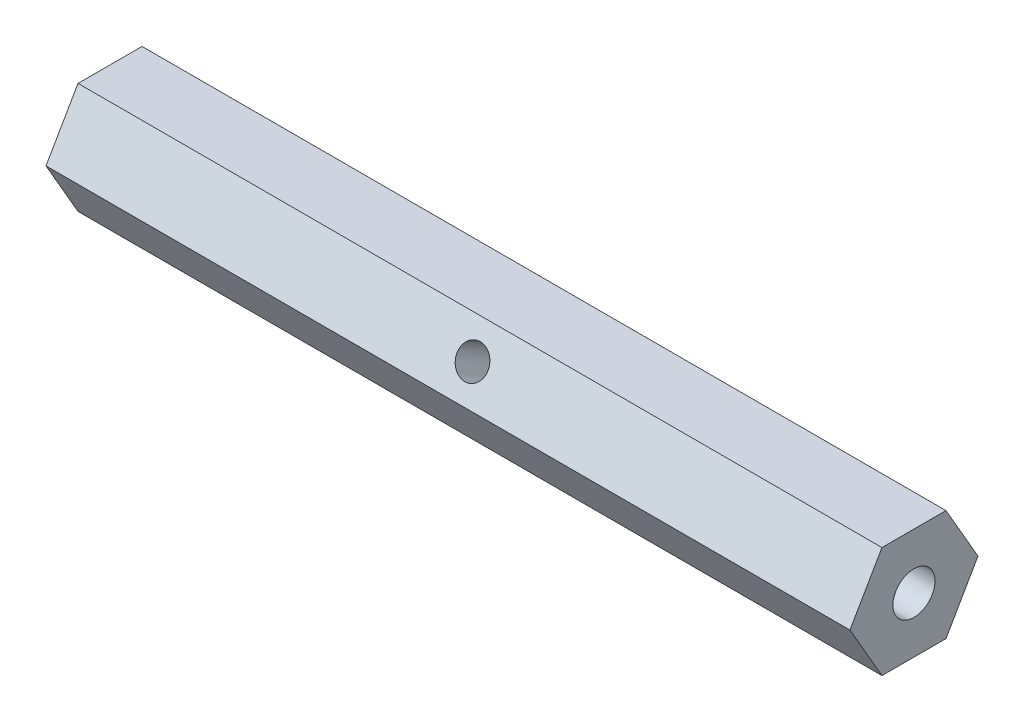
SolidWorks part; units mm, degrees
material "6061 Alloy"
ref_plane "Front" through (0, 0, 0) normal (0, 0, 1) x (1, 0, 0)
ref_plane "Top" through (0, 0, 0) normal (0, 1, 0) x (1, 0, 0)
ref_plane "Right" through (0, 0, 0) normal (1, 0, 0) x (0, 0, -1)
sketch "Sketch1" plane through (0, 0, 0) normal (1, 0, 0) x (0, 0, -1)
  line L1 (3.6662, 6.35) -> (-3.6662, 6.35)
  line L2 (-3.6662, 6.35) -> (-7.3323, 0)
  line L3 (-7.3323, 0) -> (-3.6662, -6.35)
  line L4 (-3.6662, -6.35) -> (3.6662, -6.35)
  line L5 (3.6662, -6.35) -> (7.3323, 0)
  line L6 (7.3323, 0) -> (3.6662, 6.35)
  circle A0 centre (0, 0) radius 6.35 construction
  dimension "D1" = 12.7
extrude "Boss-Extrude1" add sketch "Sketch1" along normal blind 92.075
sketch "Sketch2" plane through (92.075, 0, 0) normal (1, 0, 0) x (0, 0, -1)
  circle A0 centre (0, 0) radius 2.413
  dimension "D1" = 4.826
extrude "Cut-Extrude1" cut sketch "Sketch2" against normal blind 25.4
sketch "Sketch3" plane through (0, 3.175, 5.4993) normal (0, 0.5, 0.866) x (1, 0, 0)
  line L0 (0, 3.6662) -> (0, -3.6662) construction
  line L1 (0, 0) -> (47.0154, 0) construction
  circle A0 centre (47.0154, 0) radius 1.778
  dimension "D2" = 3.556
  dimension "D1" = 47.0154
extrude "Cut-Extrude2" cut sketch "Sketch3" against normal blind 25.4
sketch "Sketch4" [suppressed] plane through (22.352, 0, 0) normal (1, 0, 0) x (0, 0, -1)
  circle A0 centre (0, 0) radius 2.54
  dimension "D1" = 5.08
extrude "Cut-Extrude3" [suppressed] cut sketch "Sketch4" against normal through all
